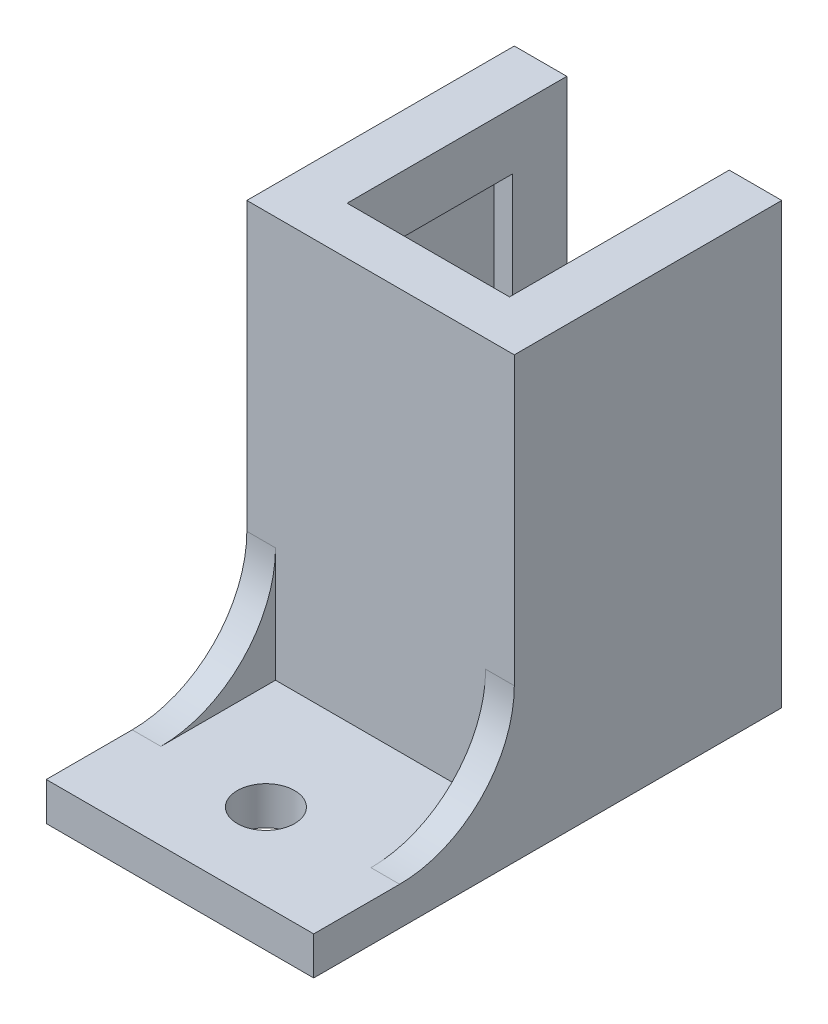
SolidWorks part; units mm, degrees
ref_plane "Front Plane" through (0, 0, 0) normal (0, 0, 1) x (1, 0, 0)
ref_plane "Top Plane" through (0, 0, 0) normal (0, 1, 0) x (1, 0, 0)
ref_plane "Right Plane" through (0, 0, 0) normal (1, 0, 0) x (0, 0, -1)
sketch "Sketch1" plane through (0, 0, 0) normal (0, 0, 1) x (1, 0, 0)
  line L1 (7, 11.5) -> (-7, 11.5)
  line L2 (7, 11.5) -> (7, -11.5)
  line L3 (7, -11.5) -> (-7, -11.5)
  line L4 (-7, 11.5) -> (-7, -11.5)
  line L5 (7, 11.5) -> (-7, -11.5) construction
  line L6 (7, -11.5) -> (-7, 11.5) construction
  point P0 (0, 0)
  dimension "D1" = 14
  dimension "D2" = 23
extrude "Boss-Extrude1" add sketch "Sketch1" along normal blind 14 contours L4 | L1 L4 L3 L2 | L2 region at (0, 0, 0)
sketch "Sketch2" plane through (0, -11.5, 0) normal (0, -1, 0) x (1, 0, 0)
  line L1 (5.2, 2.85) -> (-5.2, 2.85)
  line L2 (5.2, 2.85) -> (5.2, 11.5)
  line L3 (5.2, 11.5) -> (-5.2, 11.5)
  line L4 (-5.2, 2.85) -> (-5.2, 11.5)
  line L8 (4.25, 2.85) -> (-4.25, 2.85)
  line L9 (4.25, 2.85) -> (4.25, 0)
  line L10 (4.25, 0) -> (-4.25, 0)
  line L11 (-4.25, 2.85) -> (-4.25, 0)
  point P4 (0, 2.85)
  point P16 (0, 0)
  line M10 (7, 0) -> (7, 14)
  line M12 (-7, 14) -> (-7, 0)
  dimension "D1" = 11.5
  dimension "D2" = 8.65
  dimension "D3" = 10.4
  dimension "D4" = 8.5
extrude "Cut-Extrude1" cut sketch "Sketch2" against normal blind 20 contours L4 L1 L2 L3 | L1 L11 L9 | M10 | M12 region at (0, -11.5, 7.175) region at (0, -11.5, 1.425)
sketch "Sketch3" plane through (0, -11.5, 0) normal (0, -1, 0) x (1, 0, 0)
  line L0 (0, 20) -> (0, 14) construction
  line L1 (7, 14) -> (-7, 14)
  line L2 (7, 14) -> (7, 24.5)
  line L3 (7, 24.5) -> (-7, 24.5)
  line L4 (-7, 14) -> (-7, 24.5)
  circle A1 centre (0, 20) radius 1.5
  dimension "D1" = 3
  dimension "D2" = 6
  dimension "D3" = 4.5
extrude "Boss-Extrude2" add sketch "Sketch3" against normal blind 2
sketch "Sketch4" plane through (-7, 0, 0) normal (-1, 0, 0) x (0, 0, 1)
  line L1 (24.5, -9.5) -> (14, -9.5) construction
  line L2 (14, 11.5) -> (14, -9.5) construction
  line L3 (14, -3.5) -> (14, -9.5)
  line L4 (14, -9.5) -> (20, -9.5)
  arc A0 (20, -9.5) -> (14, -3.5) centre (20, -3.5) cw
  dimension "D1" = 6
extrude "Boss-Extrude3" add sketch "Sketch4" against normal blind 1.5
mirror "Mirror1" about plane through (0, 0, 0) normal (1, 0, 0) of "Boss-Extrude3"
sketch "Sketch5" plane through (0, 8.5, 0) normal (0, -1, 0) x (1, 0, 0)
  line L0 (5.2, 11.5) -> (-5.2, 11.5) construction
  line L1 (4.25, 0) -> (-4.25, 0)
  line L2 (4.25, 0) -> (4.25, 11.5)
  line L3 (4.25, 11.5) -> (-4.25, 11.5)
  line L4 (-4.25, 0) -> (-4.25, 11.5)
  line L5 (7, 0) -> (4.25, 0) construction
  line L6 (-4.25, 0) -> (4.25, 0) construction
extrude "Cut-Extrude2" cut sketch "Sketch5" against normal through all
sketch "Sketch6" plane through (0, 0, 0) normal (0, 0, -1) x (-1, 0, 0)
  line L0 (-7, 11.5) -> (-7, -11.5) construction
  line L1 (-7, 0) -> (7, 0)
  line L2 (-7, 0) -> (-7, -11.5)
  line L3 (-7, -11.5) -> (7, -11.5)
  line L4 (7, 0) -> (7, -11.5)
extrude "Cut-Extrude3" [suppressed] cut sketch "Sketch6" against normal through all
